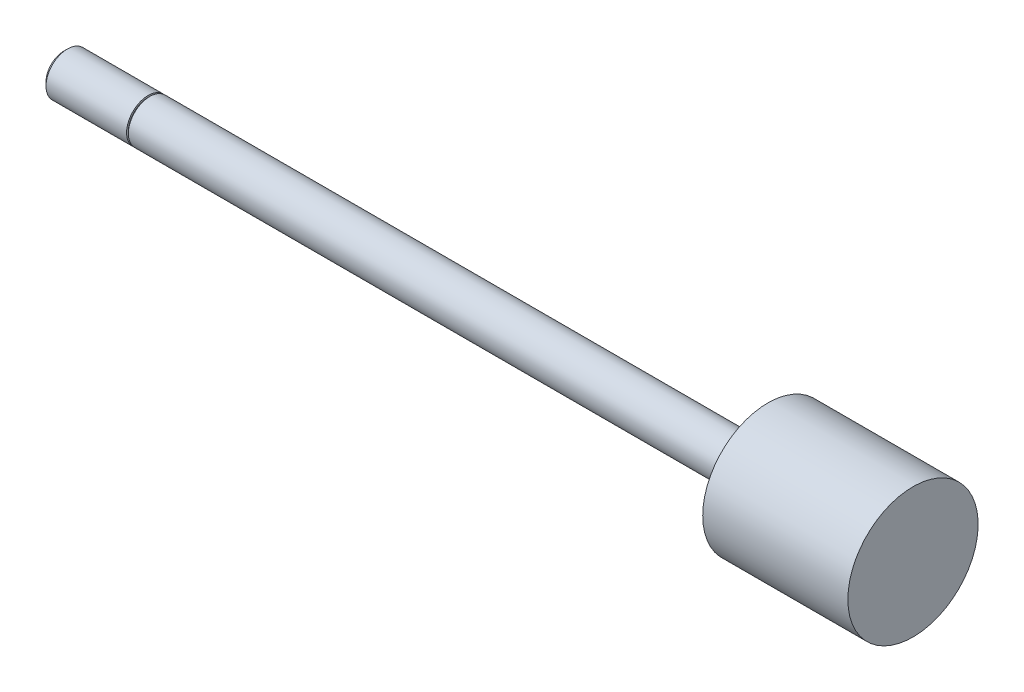
SolidWorks part; units mm, degrees
material "Plain Carbon Steel"
ref_plane "Front Plane" through (0, 0, 0) normal (0, 0, 1) x (1, 0, 0)
ref_plane "Top Plane" through (0, 0, 0) normal (0, 1, 0) x (1, 0, 0)
ref_plane "Right Plane" through (0, 0, 0) normal (1, 0, 0) x (0, 0, -1)
sketch "Sketch1" plane through (0, 0, 0) normal (0, 0, 1) x (1, 0, 0)
  line L0 (0, 0) -> (0, 3.175)
  line L1 (0, 3.175) -> (91.2876, 3.175)
  line L2 (91.2876, 3.175) -> (91.2876, 9.6203)
  line L3 (91.2876, 9.6203) -> (112.7252, 9.6203)
  line L4 (112.7252, 9.6203) -> (112.7252, 0)
  line L5 (112.7252, 0) -> (0, 0)
  line L6 (112.7252, 0) -> (0, 0) construction
revolve "Revolve1" add sketch "Sketch1" angle 360 about L6 reverse direction yes
cosmetic thread "Cosmetic Thread1" parameters "D1"=12.7, "D2"=5.268
sketch "Sketch2" plane through (0, 0, 0) normal (0, 0, 1) x (1, 0, 0)
  line L0 (-12.7, 0) -> (-12.7, 2.634)
  line L1 (-12.7, 2.634) -> (-12.159, 3.175)
  line L2 (-12.159, 3.175) -> (0, 3.175)
  line L3 (0, 3.175) -> (0, 0)
  line L4 (0, 0) -> (-12.7, 0)
  line L5 (0, 0) -> (-12.7, 0) construction
revolve "Revolve2" add sketch "Sketch2" angle 360 about L5 reverse direction yes
ref_plane "Plane1" through (0, 0, 0) normal (1, 0, 0) x (0, 0, -1)
ref_plane "Plane2" through (0, 0, 0) normal (1, 0, 0) x (0, 0, -1)
ref_plane "Plane3" through (204.0128, 0, 0) normal (1, 0, 0) x (0, 0, -1)
ref_plane "Plane4" through (-12.7, 0, 0) normal (1, 0, 0) x (0, 0, -1)
sketch "Sketch3" plane through (0, 0, 0) normal (0, 0, 1) x (1, 0, 0)
  line L0 (-0.254, 3.429) -> (-0.254, 2.921)
  line L1 (-0.254, 2.921) -> (0, 2.921)
  line L2 (0, 2.921) -> (0, 3.429)
  line L3 (0, 3.429) -> (-0.254, 3.429)
  line L4 (0, 0) -> (-0.254, 0) construction
revolve "Cut-Revolve1" cut sketch "Sketch3" angle 360 about L4 reverse direction yes
ref_plane "Plane5" through (0, 0, 0) normal (1, 0, 0) x (0, 0, -1)
ref_plane "Plane6" through (-16.764, 0, 0) normal (1, 0, 0) x (0, 0, -1)
ref_plane "dia1 XY" through (0, 0, 0) normal (1, 0, 0) x (0, 0, -1)
ref_plane "dia1 XZ" through (0, 3.175, 0) normal (0, -1, 0) x (-1, 0, 0)
ref_plane "dia1 YZ" through (0, 0, 0) normal (0, 0, -1) x (-1, 0, 0)
ref_axis "dia1 X" through (0, 3.175, 80.9) along (0, 0, -1)
ref_axis "dia1 Y" through (0, -50, 0) along (0, 1, 0)
ref_axis "dia1 Z" through (80.9, 3.175, 0) along (-1, 0, 0)
sketch3d "dia1"
  point P0 (0, 3.175, 0)
ref_plane "dia12 XY" through (0, 0, 0) normal (1, 0, 0) x (0, 0, -1)
ref_plane "dia12 XZ" through (0, 0, 0) normal (0, -1, 0) x (-1, 0, 0)
ref_plane "dia12 YZ" through (0, 0, 10.9537) normal (0, 0, -1) x (-1, 0, 0)
ref_axis "dia12 X" through (0, 0, 80.9) along (0, 0, -1)
ref_axis "dia12 Y" through (0, -50, 10.9537) along (0, 1, 0)
ref_axis "dia12 Z" through (80.9, 0, 10.9537) along (-1, 0, 0)
sketch3d "dia12"
  point P0 (0, 0, 10.9537)
ref_plane "dia2 XY" through (0, 0, 0) normal (1, 0, 0) x (0, 0, -1)
ref_plane "dia2 XZ" through (0, -3.175, 0) normal (0, -1, 0) x (-1, 0, 0)
ref_plane "dia2 YZ" through (0, 0, 0) normal (0, 0, -1) x (-1, 0, 0)
ref_axis "dia2 X" through (0, -3.175, 80.9) along (0, 0, -1)
ref_axis "dia2 Y" through (0, -50, 0) along (0, 1, 0)
ref_axis "dia2 Z" through (80.9, -3.175, 0) along (-1, 0, 0)
sketch3d "dia2"
  point P0 (0, -3.175, 0)
ref_plane "dia22 XY" through (0, 0, 0) normal (1, 0, 0) x (0, 0, -1)
ref_plane "dia22 XZ" through (0, 0, 0) normal (0, -1, 0) x (-1, 0, 0)
ref_plane "dia22 YZ" through (0, 0, -10.9537) normal (0, 0, -1) x (-1, 0, 0)
ref_axis "dia22 X" through (0, 0, 80.9) along (0, 0, -1)
ref_axis "dia22 Y" through (0, -50, -10.9537) along (0, 1, 0)
ref_axis "dia22 Z" through (80.9, 0, -10.9537) along (-1, 0, 0)
sketch3d "dia22"
  point P0 (0, 0, -10.9537)
ref_plane "rl1 XY" through (-12.7, 0, 0) normal (1, 0, 0) x (0, 0, -1)
ref_plane "rl1 XZ" through (0, 0, 0) normal (0, -1, 0) x (-1, 0, 0)
ref_plane "rl1 YZ" through (0, 0, 0) normal (0, 0, -1) x (-1, 0, 0)
ref_axis "rl1 X" through (-12.7, 0, 80.9) along (0, 0, -1)
ref_axis "rl1 Y" through (-12.7, -50, 0) along (0, 1, 0)
ref_axis "rl1 Z" through (80.9, 0, 0) along (-1, 0, 0)
sketch3d "rl1"
  point P0 (-12.7, 0, 0)
ref_plane "rl2 XY" through (0, 0, 0) normal (1, 0, 0) x (0, 0, -1)
ref_plane "rl2 XZ" through (0, 0, 0) normal (0, -1, 0) x (-1, 0, 0)
ref_plane "rl2 YZ" through (0, 0, 0) normal (0, 0, -1) x (-1, 0, 0)
ref_axis "rl2 X" through (0, 0, 80.9) along (0, 0, -1)
ref_axis "rl2 Y" through (0, -50, 0) along (0, 1, 0)
ref_axis "rl2 Z" through (80.9, 0, 0) along (-1, 0, 0)
sketch3d "rl2"
  point P0 (0, 0, 0)
ref_plane "rod_cp XY" through (0, 0, 0) normal (1, 0, 0) x (0, 0, -1)
ref_plane "rod_cp XZ" through (0, 0, 0) normal (0, -1, 0) x (-1, 0, 0)
ref_plane "rod_cp YZ" through (0, 0, 0) normal (0, 0, -1) x (-1, 0, 0)
ref_axis "rod_cp X" through (0, 0, 80.9) along (0, 0, -1)
ref_axis "rod_cp Y" through (0, -50, 0) along (0, 1, 0)
ref_axis "rod_cp Z" through (80.9, 0, 0) along (-1, 0, 0)
sketch3d "rod_cp"
  point P0 (0, 0, 0)
ref_plane "thd1 XY" through (-12.7, 0, 0) normal (1, 0, 0) x (0, 0, -1)
ref_plane "thd1 XZ" through (0, 3.175, 0) normal (0, -1, 0) x (-1, 0, 0)
ref_plane "thd1 YZ" through (0, 0, 0) normal (0, 0, -1) x (-1, 0, 0)
ref_axis "thd1 X" through (-12.7, 3.175, 80.9) along (0, 0, -1)
ref_axis "thd1 Y" through (-12.7, -50, 0) along (0, 1, 0)
ref_axis "thd1 Z" through (80.9, 3.175, 0) along (-1, 0, 0)
sketch3d "thd1"
  point P0 (-12.7, 3.175, 0)
ref_plane "thd2 XY" through (-12.7, 0, 0) normal (1, 0, 0) x (0, 0, -1)
ref_plane "thd2 XZ" through (0, -3.175, 0) normal (0, -1, 0) x (-1, 0, 0)
ref_plane "thd2 YZ" through (0, 0, 0) normal (0, 0, -1) x (-1, 0, 0)
ref_axis "thd2 X" through (-12.7, -3.175, 80.9) along (0, 0, -1)
ref_axis "thd2 Y" through (-12.7, -50, 0) along (0, 1, 0)
ref_axis "thd2 Z" through (80.9, -3.175, 0) along (-1, 0, 0)
sketch3d "thd2"
  point P0 (-12.7, -3.175, 0)
ref_plane "to_rod_clevis XY" through (-16.764, 0, 0) normal (1, 0, 0) x (0, 0, -1)
ref_plane "to_rod_clevis XZ" through (0, 0, 0) normal (0, -1, 0) x (-1, 0, 0)
ref_plane "to_rod_clevis YZ" through (0, 0, 0) normal (0, 0, -1) x (-1, 0, 0)
ref_axis "to_rod_clevis X" through (-16.764, 0, 80.9) along (0, 0, -1)
ref_axis "to_rod_clevis Y" through (-16.764, -50, 0) along (0, 1, 0)
ref_axis "to_rod_clevis Z" through (80.9, 0, 0) along (-1, 0, 0)
sketch3d "to_rod_clevis"
  point P0 (-16.764, 0, 0)
